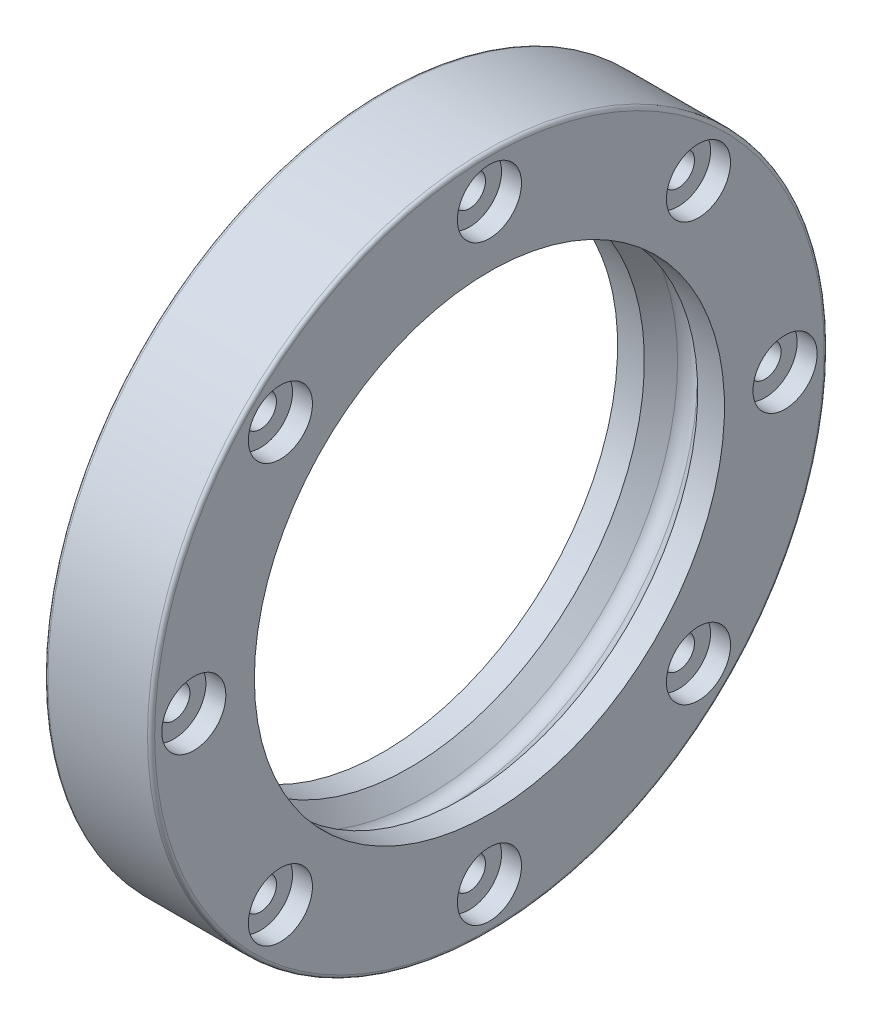
SolidWorks part; units mm, degrees
ref_plane "Front Plane" through (0, 0, 0) normal (0, 0, 1) x (1, 0, 0)
ref_plane "Top Plane" through (0, 0, 0) normal (0, 1, 0) x (1, 0, 0)
ref_plane "Right Plane" through (0, 0, 0) normal (1, 0, 0) x (0, 0, -1)
sketch "Sketch1" plane through (0, 0, 0) normal (0, 0, 1) x (1, 0, 0)
  line L0 (-33.7322, 0) -> (0, 0) construction
  line L1 (0, 0) -> (0, 40.25) construction
  line L2 (0, 36.7426) -> (4.2426, 32.5)
  line L3 (7.5, 47.5) -> (-7.5, 47.5)
  line L4 (7.5, 47.5) -> (7.5, 33)
  line L5 (7.5, 33) -> (-7.5, 33)
  line L6 (-7.5, 47.5) -> (-7.5, 33)
  line L7 (7.5, 47.5) -> (-7.5, 33) construction
  line L8 (7.5, 33) -> (-7.5, 47.5) construction
  line L9 (7.5, 32) -> (-7.5, 32) construction
  line L10 (7.5, 32) -> (7.5, 17.5) construction
  line L11 (7.5, 17.5) -> (-7.5, 17.5) construction
  line L12 (-7.5, 32) -> (-7.5, 17.5) construction
  line L13 (7.5, 32) -> (-7.5, 17.5) construction
  line L14 (7.5, 17.5) -> (-7.5, 32) construction
  line L15 (0, 36.7426) -> (-4.2426, 32.5)
  line L16 (4.2426, 32.5) -> (0, 28.2574)
  line L17 (-4.2426, 32.5) -> (0, 28.2574)
  line L18 (0, 36.7426) -> (0, 28.2574) construction
  line L19 (4.2426, 32.5) -> (-4.2426, 32.5) construction
  point P9 (0, 24.75)
  point P15 (0, 32.5)
  dimension "D1" = 17.5
  dimension "D2" = 47.5
  dimension "D3" = 15
  dimension "D4" = 14.5
  dimension "D5" = 0.5
  dimension "D6" = 6
revolve "Revolve1" add sketch "Sketch1" angle 360 about L0 region at (0, 40.6632, 0)
ref_axis "Axis1" through (7.5, 0, 0) along (-1, 0, 0)
fillet "Fillet1" radius 2 1 edges at (0, 0, 36.7426)
fillet "Fillet2" radius 0.5 2 edges at (7.5, 0, 47.5) (-7.5, 0, 47.5)
sketch "Sketch2" plane through (7.5, 0, 0) normal (1, 0, 0) x (0, 0, -1)
  line L0 (0, 0) -> (0, 41.5) construction
  circle A0 centre (0, 0) radius 41.5 construction
  dimension "D1" = 83
hole_wizard "CBORE for M4 Hex Head Cap Screw1" positions "3DSketch2" profile "Sketch3" counterbore size "M4" standard "ISO" end condition through all
sketch3d "3DSketch2"
  point P0 (7.5, 41.5, 0)
sketch "Sketch3" plane through (7.5, 41.5, 0) normal (0, 1, 0) x (0, 0, -1)
  line L0 (0, 0) -> (0, 15)
  line L1 (0, 15) -> (2.25, 15)
  line L3 (2.25, 15) -> (2.25, 2.8)
  line L4 (2.25, 2.8) -> (4.5, 2.8)
  line L5 (4.5, 2.8) -> (4.5, 0)
  line L7 (4.5, 0) -> (0, 0)
  line L11 (0, -6.35) -> (0, 107.95) construction
  dimension "Thru Hole Dia." = 4.5
  dimension "Thru Hole Depth" = 15
  dimension "C'Bore Dia." = 9
  dimension "C'Bore Depth" = 2.8
pattern_circular "CirPattern1" count 8 over 360 about axis through (7.5, 0, 0) along (-1, 0, 0) of "CBORE for M4 Hex Head Cap Screw1"
